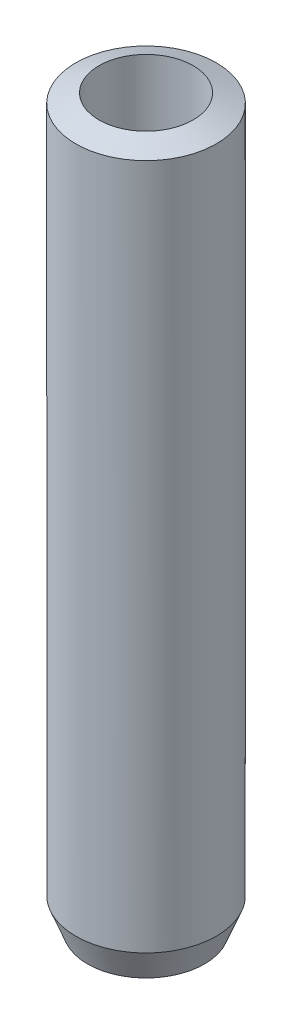
SolidWorks part; units mm, degrees
ref_plane "Front Plane" through (0, 0, 0) normal (0, 0, 1) x (1, 0, 0)
ref_plane "Top Plane" through (0, 0, 0) normal (0, 1, 0) x (1, 0, 0)
ref_plane "Right Plane" through (0, 0, 0) normal (1, 0, 0) x (0, 0, -1)
sketch "Sketch1" plane through (0, 0, 0) normal (0, 1, 0) x (1, 0, 0)
  circle A0 centre (0, 0) radius 20
  dimension "SHAFT_OD" = 40
extrude "Boss-Extrude1" add sketch "Sketch1" along normal blind 207.198
sketch "Sketch2" plane through (0, 0, 0) normal (0, 1, 0) x (1, 0, 0)
  circle A0 centre (0, 0) radius 13.3997
  dimension "BORE_D" = 26.7994
extrude "Cut-Extrude1" cut sketch "Sketch2" along normal through all
chamfer "Chamfer1" distance 3.3496 angle 68.577 2 edges at (0, 207.198, 20) (0, 0, 20) first distance on face at (0, 207.198, 20) first distance on face at (0, 0, 13.3997)
